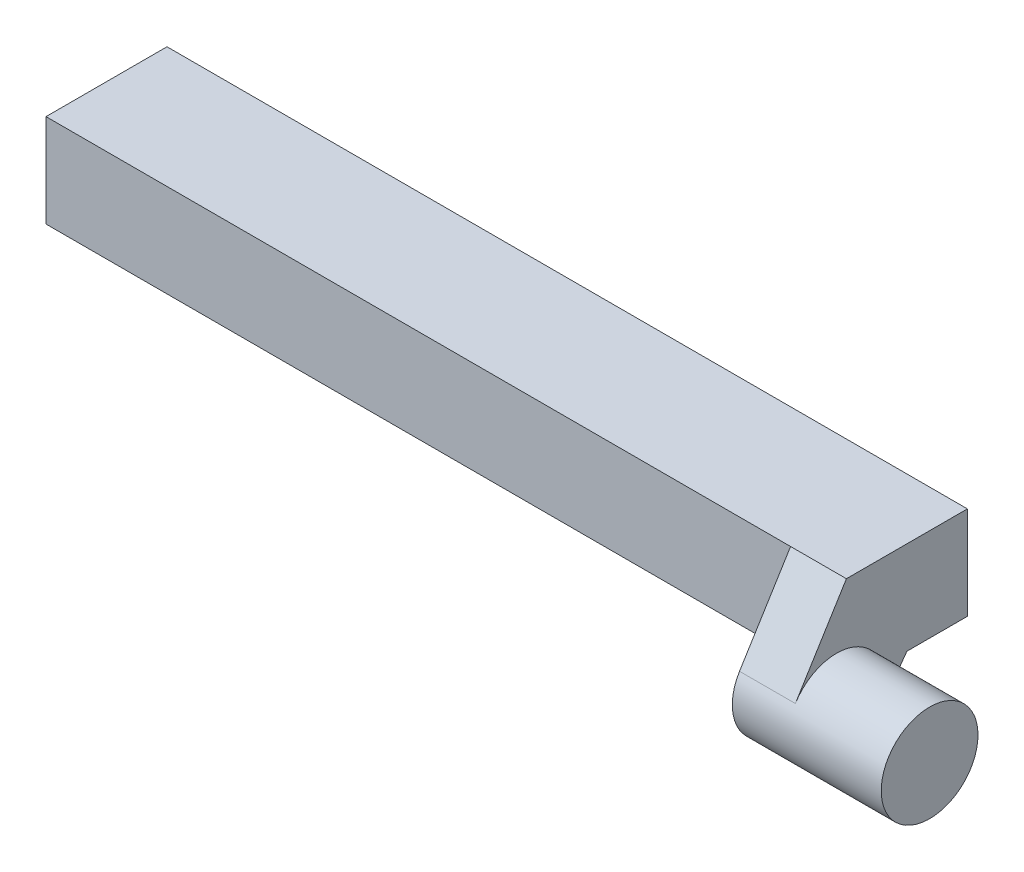
SolidWorks part; units mm, degrees
ref_plane "Front Plane" through (0, 0, 0) normal (0, 0, 1) x (1, 0, 0)
ref_plane "Top Plane" through (0, 0, 0) normal (0, 1, 0) x (1, 0, 0)
ref_plane "Right Plane" through (0, 0, 0) normal (1, 0, 0) x (0, 0, -1)
sketch "Sketch2" plane through (0, 0, 0) normal (1, 0, 0) x (0, 0, -1)
  line L1 (-2.25, -2.25) -> (2.25, -2.25)
  line L2 (-2.25, -2.25) -> (-2.25, 2.25)
  line L3 (-2.25, 2.25) -> (2.25, 2.25)
  line L4 (2.25, -2.25) -> (2.25, 2.25)
  line L5 (-2.25, -2.25) -> (2.25, 2.25) construction
  line L6 (-2.25, 2.25) -> (2.25, -2.25) construction
  line L7 (3.25, -2.5) -> (-3.25, -2.5)
  line L8 (3.25, -2.5) -> (3.25, 2.5)
  line L9 (3.25, 2.5) -> (-3.25, 2.5)
  line L10 (-3.25, -2.5) -> (-3.25, 2.5)
  line L11 (3.25, -2.5) -> (-3.25, 2.5) construction
  line L12 (3.25, 2.5) -> (-3.25, -2.5) construction
  point P0 (0, 0)
  point P5 (0, 0)
  dimension "D1" = 4.5
  dimension "D2" = 4.5
  dimension "D3" = 6.5
  dimension "D4" = 5
extrude "Boss-Extrude1" add sketch "Sketch2" along normal blind 2
extrude "Boss-Extrude2" add sketch "Sketch2<2>" along normal blind 38 from surface contours L1 L4 L3 L2 | L10 L7 L8 L9 L4 L1 L2 L3 region at (0, 0, 0) region at (0, -2.418, 0) starting at face at (2, 0, 0)
sketch "Sketch2<2>" plane through (0, 0, 0) normal (1, 0, 0) x (0, 0, -1) same geometry as "Sketch2"
sketch "Sketch5" plane through (40, 0, 0) normal (1, 0, 0) x (0, 0, -1)
  line L0 (-0.02, -0.4959) -> (-4.75, -0.4959) construction
  line L5 (-5.9921, -1.9359) -> (-3.25, 2.5)
  line L6 (-3.25, 2.5) -> (3.25, 2.5)
  line L7 (3.25, 2.5) -> (3.25, -2.5)
  line L8 (3.25, -2.5) -> (0, -2.5)
  line L9 (-3.25, -2.5) -> (3.25, -2.5) construction
  line L10 (0, -2.5) -> (-1.67, -4.8214)
  arc A1 (-5.9921, -1.9359) -> (-1.67, -4.8214) centre (-3.7806, -3.303) ccw
  dimension "D2" = 2.6
  dimension "D1" = 4.73
extrude "Boss-Extrude3" add sketch "Sketch5" along normal blind 3
sketch "Sketch6" plane through (43, 0, 0) normal (1, 0, 0) x (0, 0, -1)
  circle A1 centre (-3.7806, -3.303) radius 2.6
  dimension "D1" = 5.2
extrude "Boss-Extrude4" add sketch "Sketch6" along normal blind 5
